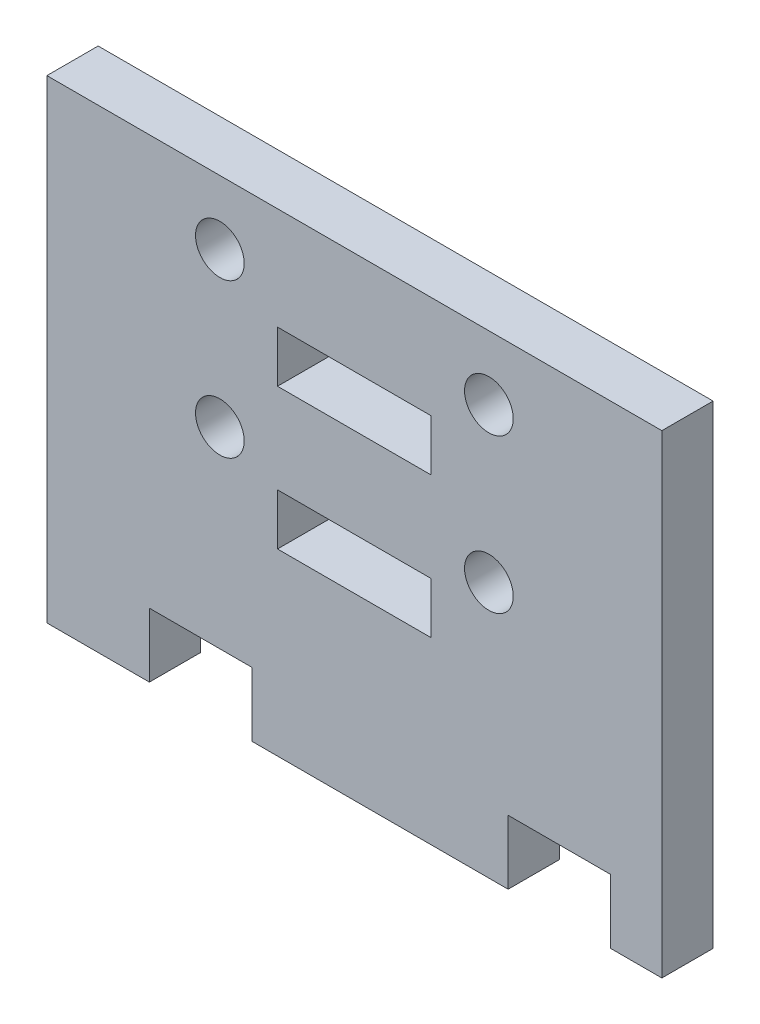
SolidWorks part; units mm, degrees
ref_plane "Front Plane" through (0, 0, 0) normal (0, 0, 1) x (1, 0, 0)
ref_plane "Top Plane" through (0, 0, 0) normal (0, 1, 0) x (1, 0, 0)
ref_plane "Right Plane" through (0, 0, 0) normal (1, 0, 0) x (0, 0, -1)
sketch "Sketch1" plane through (0, 0, 0) normal (0, 0, 1) x (1, 0, 0)
  line L0 (4, 2.5) -> (8, 2.5)
  line L1 (4, 0) -> (0, 0)
  line L2 (0, 18.5) -> (24, 18.5)
  line L3 (0, 0) -> (0, 18.5)
  line L4 (9, 14.5) -> (9, 12.5)
  line L5 (15, 14.5) -> (9, 14.5)
  line L6 (9, 12.5) -> (15, 12.5)
  line L7 (15, 12.5) -> (15, 14.5)
  line L8 (4, 2.5) -> (4, 0)
  line L9 (22, 0) -> (24, 0)
  line L10 (24, 0) -> (24, 18.5)
  line L11 (18, 0) -> (18, 2.5)
  line L12 (15, 7) -> (15, 9)
  line L13 (9, 7) -> (15, 7)
  line L14 (22, 2.5) -> (22, 0)
  line L15 (15, 9) -> (9, 9)
  line L16 (9, 9) -> (9, 7)
  line L17 (18, 2.5) -> (22, 2.5)
  line L18 (8, 0) -> (8, 2.5)
  line L19 (8, 0) -> (18, 0)
  line L20 (12, 12.5) -> (12, 9) construction
  circle A0 centre (6.75, 16) radius 0.95
  circle A1 centre (17.25, 10) radius 0.95
  circle A2 centre (17.25, 16) radius 0.95
  circle A3 centre (6.75, 10) radius 0.95
  dimension "D1" = 1.9
  dimension "D2" = 4
  dimension "D3" = 18
  dimension "D4" = 2.5
  dimension "D5" = 2
  dimension "D6" = 7
  dimension "D7" = 9
  dimension "D8" = 12.5
  dimension "D9" = 15
  dimension "D10" = 6
  dimension "D11" = 10
  dimension "D12" = 18.5
  dimension "D13" = 10.5
extrude "Boss-Extrude1" add sketch "Sketch1" along normal blind 2
equation "\"D13@Sketch1\"= \"fingerWidth@parametersSketch@prostheticParameters.SLDPRT\" - 5.7'Hole distance"
equation "\"D1@Sketch1\"= 1.5 + \"tol1@parametersSketch@prostheticParameters.SLDPRT\""
